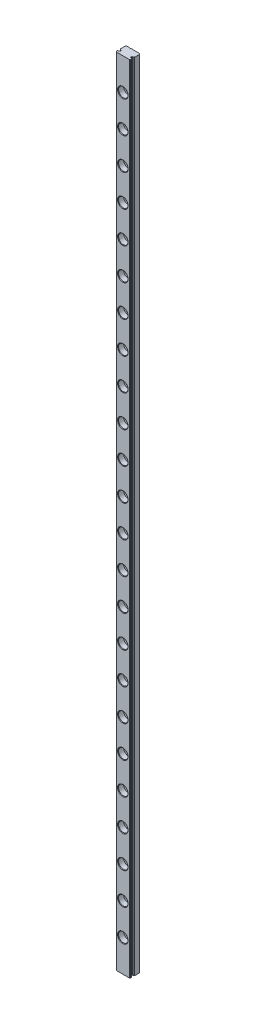
SolidWorks part; units mm, degrees
ref_plane "Horní rovina" through (0, 0, 0) normal (0, 0, 1) x (1, 0, 0)
ref_plane "Přední rovina" through (0, 0, 0) normal (0, 1, 0) x (1, 0, 0)
ref_plane "Pravá rovina" through (0, 0, 0) normal (1, 0, 0) x (0, 0, -1)
sketch "Skica1" plane through (0, 0, 0) normal (0, 1, 0) x (1, 0, 0)
  line L17 (0, -14.9046) -> (0, 0) construction
  line L22 (3.3, -4.5) -> (0, -4.5) construction
  line L23 (-4.1, -6.5) -> (4.1, -6.5)
  line L24 (4.1, -6.5) -> (4.5, -6.1)
  line L25 (4.5, -6.1) -> (4.5, -5.4539)
  line L26 (3.9045, -4.945) -> (3.3, -4.89)
  line L27 (3.3, -4.89) -> (3.3, -4.11)
  line L28 (3.3, -4.11) -> (3.9095, -4.045)
  line L29 (4.5, -3.5461) -> (4.5, -0.4)
  line L30 (4.5, -0.4) -> (4.1, 0)
  line L31 (4.1, 0) -> (-1.4, 0)
  line L32 (-2.2, 0) -> (-4.1, 0)
  line L33 (-4.1, 0) -> (-4.5, -0.4)
  line L34 (-4.5, -0.4) -> (-4.5, -3.5461)
  line L38 (-4.5, -5.4539) -> (-4.5, -6.1)
  line L39 (-4.5, -6.1) -> (-4.1, -6.5)
  line L40 (-3.3, -4.11) -> (-3.9095, -4.045)
  line L41 (-3.3, -4.89) -> (-3.3, -4.11)
  line L42 (-3.9045, -4.945) -> (-3.3, -4.89)
  arc A7 (3.9045, -4.945) -> (4.5, -5.4539) centre (4.8, -4.5) ccw
  arc A8 (4.5, -3.5461) -> (3.9095, -4.045) centre (4.8, -4.5) ccw
  arc A9 (-2.2, 0) -> (-1.4, 0) centre (-1.8, 0.3) ccw
  arc A12 (-4.5, -3.5461) -> (-3.9095, -4.045) centre (-4.8, -4.5) cw
  arc A13 (-3.9045, -4.945) -> (-4.5, -5.4539) centre (-4.8, -4.5) cw
  point P4 (0, -6.5)
  dimension "D7" = 1
  dimension "D19" = 0.5
  dimension "D2" = 8.2
  dimension "D1" = 4.5
  dimension "D4" = 6.5
  dimension "D5" = 0.3
  dimension "D6" = 2
  dimension "D8" = 0.78
  dimension "D9" = 0.9
  dimension "D10" = 1.2
  dimension "D12" = 0.4
  dimension "D13" = 0.4
  dimension "D15" = 0.4
  dimension "D16" = 0.4
  dimension "D17" = 0.3
  dimension "D18" = 1.8
extrude "Delka" add sketch "Skica1" along normal blind 500
hole_wizard "Díra1" positions "Skica3" profile "Skica4" legacy end condition through all
sketch "Skica3" plane through (0, 0, 6.5) normal (0, 0, 1) x (1, 0, 0)
  point P0 (0, 20)
  point P2 (0, 20)
  dimension "D1" = 20
sketch "Skica4" plane through (0, 20, 6.5) normal (1, 0, 0) x (0, -1, 0)
  line L0 (0, 0) -> (0, 6.6576)
  line L1 (0, 6.6576) -> (1.75, 6.6576)
  line L2 (1.75, 6.6576) -> (1.75, 3.5)
  line L3 (1.75, 3.5) -> (3, 3.5)
  line L4 (3, 3.5) -> (3, 0)
  line L5 (3, 0) -> (0, 0)
  line L6 (0, 110) -> (0, -10) construction
  dimension "Průměr" = 3.5
  dimension "Hloubka" = 6.6576
  dimension "Průměr válc. zahloubení" = 6
  dimension "Hloubka válc. zahloubení" = 3.5
chamfer "Zkosení1" distance 0.3 angle 45 2 edges at (1.75, 20, 0) (3, 20, 6.5)
pattern_linear "LinPole1" count 24 spacing 20 along (0, 1, 0) of "Díra1", "Zkosení1"
equation "\"P\"= 20mm"
equation "\"Emin\"= 8mm"
equation "\"Emax\"= 20mm"
equation "\"Hc\"= round (  ( \"D1@Delka\" - 2 * \"Emin\" )  / \"P\" ) "
equation "\"E\"= ( \"L\" - ( ( \"Hc\" - 1 ) * \"P\" ) ) / 2"
equation "\"L\"=500"
equation "\"D1@Delka\" = \"L\""
equation "\"D1@LinPole1\"= \"Hc\""
equation "\"D3@LinPole1\"= \"P\""
equation "\"D1@Skica3\"= \"E\""
equation "\"Přidat vysunutím1\"= \"L\""
equation "\"Delka\"= \"L\""
equation "\"D13@Skica1\"=\"D12@Skica1\""
equation "\"D15@Skica1\"=\"D12@Skica1\""
equation "\"D16@Skica1\"=\"D12@Skica1\""
